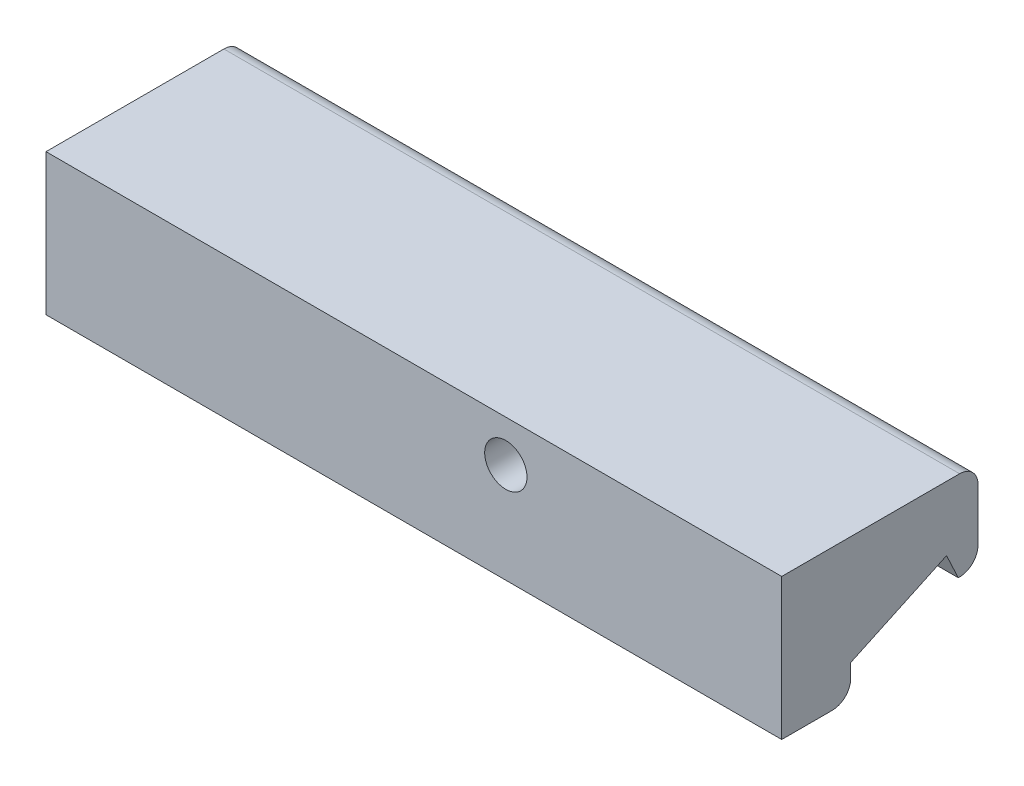
SolidWorks part; units mm, degrees
ref_plane "Front Plane" through (0, 0, 0) normal (0, 0, 1) x (1, 0, 0)
ref_plane "Top Plane" through (0, 0, 0) normal (0, 1, 0) x (1, 0, 0)
ref_plane "Right Plane" through (0, 0, 0) normal (1, 0, 0) x (0, 0, -1)
sketch "Sketch1" plane through (0, 0, 0) normal (1, 0, 0) x (0, 0, -1)
  line L0 (0, 0) -> (5.4995, 0)
  line L2 (21.3407, 7.6355) -> (21.3407, 13.3601)
  line L3 (19.3407, 15.3601) -> (0, 15.3601)
  line L4 (0, 15.3601) -> (0, 0)
  line L6 (19.1904, 5.6412) -> (17.9225, 8.3601)
  line L7 (17.9225, 8.3601) -> (7.5, 3.5)
  line L8 (7.5, 3.5) -> (7.5, 2.0005)
  arc A0 (19.3407, 15.3601) -> (21.3407, 13.3601) centre (19.3407, 13.3601) cw
  arc A1 (19.1904, 5.6412) -> (21.3407, 7.6355) centre (19.3407, 7.6355) ccw
  arc A2 (5.4995, 0) -> (7.5, 2.0005) centre (5.4995, 2.0005) ccw
  dimension "D7" = 4
  dimension "D8" = 4.0011
  dimension "D3" = 11.5
  dimension "D1" = 7.5
  dimension "D5" = 7
  dimension "D6" = 3
extrude "ProfileBoss-Extrude1" add sketch "Sketch1" along normal blind 80
sketch "Sketch2" plane through (0, 0.0022, 0.001) normal (0, -0.9063, -0.4226) x (1, 0, 0)
  line L1 (0, -8.2765) -> (0, -19.7765) construction
  line L2 (80, -8.2765) -> (0, -8.2765) construction
  circle A0 centre (36.15, -14.0265) radius 2.3
  dimension "D1" = 4.6
  dimension "D2" = 5.75
  dimension "D3" = 36.15
extrude "LedStripMountHolesCut-Extrude1" cut sketch "Sketch2" against normal blind 4.5
sketch "Sketch3" plane through (0, 0, 0) normal (0, 0, 1) x (1, 0, 0)
  circle A0 centre (50, 10.8601) radius 2.3
  dimension "D1" = 4.6
  dimension "D4" = 4.5
  dimension "D2" = 50
extrude "MountingHolesCut-Extrude3" cut sketch "Sketch3" against normal blind 4.5
equation "\"LightStripShortLength\"= 80mm"
equation "\"D1@ProfileBoss-Extrude1\"=\"LightStripShortLength\""
equation "\"LightStripWidth\"= 11.5mm'Spec"
equation "\"D3@Sketch1\"=\"LightStripWidth\""
equation "\"D2@Sketch2\"=\"LightStripWidth\"/2"
equation "\"LightStripMountHoleFromLeftOrRightEdge\"= ( \"LightStripLength\" - \"LightStripDistanceBetween<MountingHoles\" ) / 2"
equation "\"LightStripGuideMountingHoleFromLeftOrRightSide\"= 50mm"
equation "\"LightStripGuideMountingHoleFromTop\"= 4.5mm"
equation "\"D4@Sketch3\"=\"LightStripGuideMountingHoleFromTop\""
equation "\"D3@Sketch2\"=\"LightStripMountHoleFromLeftOrRightEdge\""
equation "\"D2@Sketch3\"=\"LightStripGuideMountingHoleFromLeftOrRightSide\""
equation "\"LightStripLength\"= 270mm'From Step file"
equation "\"LightStripDistanceBetween<MountingHoles\"= 197.7mm'From Step file"
